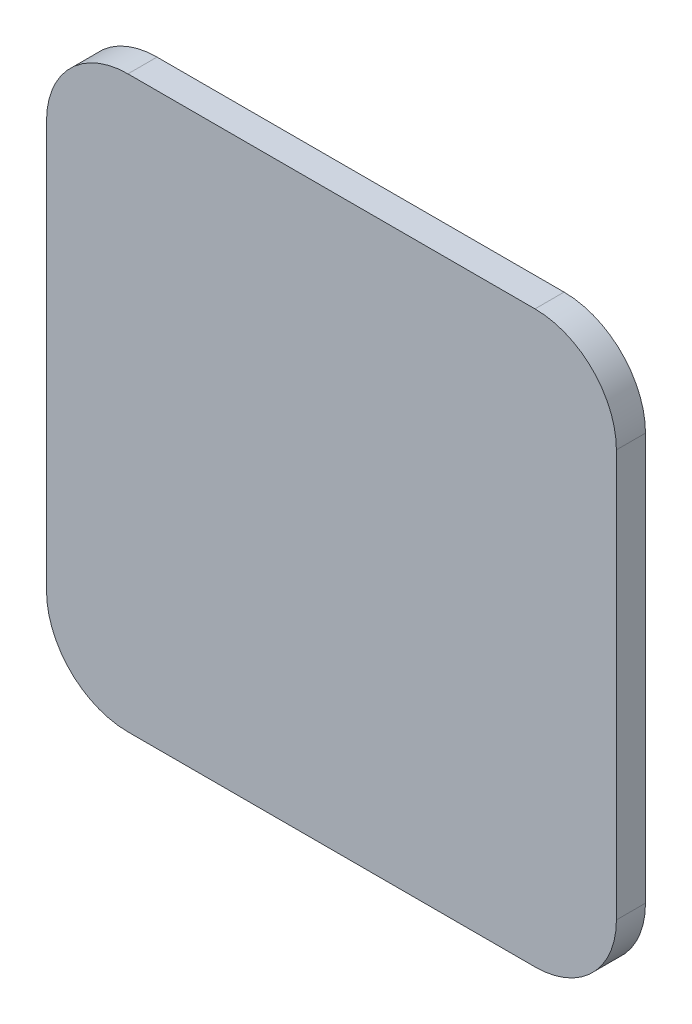
SolidWorks part; units mm, degrees
ref_plane "Front Plane" through (0, 0, 0) normal (0, 0, 1) x (1, 0, 0)
ref_plane "Top Plane" through (0, 0, 0) normal (0, 1, 0) x (1, 0, 0)
ref_plane "Right Plane" through (0, 0, 0) normal (1, 0, 0) x (0, 0, -1)
sketch "Sketch1" plane through (0, 0, 0) normal (0, 0, 1) x (1, 0, 0)
  line L0 (9.5027, -49.53) -> (9.5027, -31.75) construction
  line L1 (5.6927, -27.94) -> (-12.0873, -27.94) construction
  line L2 (5.6927, -53.34) -> (-12.0873, -53.34)
  line L3 (9.5027, -49.53) -> (9.5027, -31.75)
  line L4 (5.6927, -27.94) -> (-12.0873, -27.94)
  line L5 (-15.8973, -31.75) -> (-15.8973, -49.53)
  line L10 (6.5817, -49.53) -> (6.5817, -31.75)
  line L11 (5.6927, -30.861) -> (-12.0873, -30.861)
  line L12 (-12.9763, -31.75) -> (-12.9763, -49.53)
  line L13 (5.6927, -50.419) -> (-12.0873, -50.419)
  line L14 (5.6927, -28.194) -> (-12.0873, -28.194)
  line L15 (-15.6433, -31.75) -> (-15.6433, -49.53)
  line L16 (5.6927, -53.086) -> (-12.0873, -53.086)
  line L17 (9.2487, -49.53) -> (9.2487, -31.75)
  arc A0 (5.6927, -53.34) -> (9.5027, -49.53) centre (5.6927, -49.53) ccw
  arc A1 (9.5027, -31.75) -> (5.6927, -27.94) centre (5.6927, -31.75) ccw
  arc A2 (-12.0873, -27.94) -> (-15.8973, -31.75) centre (-12.0873, -31.75) ccw
  arc A3 (-12.0873, -27.94) -> (-15.8973, -31.75) centre (-12.0873, -31.75) ccw construction
  arc A4 (-12.0873, -53.34) -> (-15.8973, -49.53) centre (-12.0873, -49.53) cw
  arc A5 (-15.8973, -49.53) -> (-12.0873, -53.34) centre (-12.0873, -49.53) ccw construction
  arc A10 (6.5817, -31.75) -> (5.6927, -30.861) centre (5.6927, -31.75) ccw
  arc A11 (-12.0873, -30.861) -> (-12.9763, -31.75) centre (-12.0873, -31.75) ccw
  arc A12 (-12.0873, -50.419) -> (-12.9763, -49.53) centre (-12.0873, -49.53) cw
  arc A13 (5.6927, -50.419) -> (6.5817, -49.53) centre (5.6927, -49.53) ccw
  arc A14 (9.2487, -31.75) -> (5.6927, -28.194) centre (5.6927, -31.75) ccw
  arc A15 (-12.0873, -28.194) -> (-15.6433, -31.75) centre (-12.0873, -31.75) ccw
  arc A16 (-12.0873, -53.086) -> (-15.6433, -49.53) centre (-12.0873, -49.53) cw
  arc A17 (5.6927, -53.086) -> (9.2487, -49.53) centre (5.6927, -49.53) ccw
  dimension "D1" = 2.921
  dimension "D2" = 0.254
extrude "Boss-Extrude1" add sketch "Sketch1" against normal blind 1.27 contours L16 A17 L17 A14 L14 A15 L15 A16 A13 L13 A12 L12 A11 L11 A10 L10 region at (7.9583, -29.4844, 0)
extrude "Boss-Extrude2" add sketch "Sketch1<3>" against normal blind 2.54 contours L13 A13 L10 A10 L11 A11 L12 A12 region at (-3.1973, -40.64, 0)
sketch "Sketch1<3>" plane through (0, 0, 0) normal (0, 0, 1) x (1, 0, 0) same geometry as "Sketch1"
sketch "Sketch2" plane through (0, 0, -2.54) normal (0, 0, -1) x (-1, 0, 0)
  line L0 (12.0873, -30.861) -> (-5.6927, -30.861)
  line L1 (-6.5817, -31.75) -> (-6.5817, -49.53)
  line L2 (-5.6927, -50.419) -> (12.0873, -50.419)
  line L3 (12.9763, -49.53) -> (12.9763, -31.75)
  line L4 (11.7063, -49.149) -> (11.7063, -32.131)
  line L5 (11.7063, -32.131) -> (-5.3117, -32.131)
  line L6 (-5.3117, -32.131) -> (-5.3117, -49.149)
  line L7 (-5.3117, -49.149) -> (11.7063, -49.149)
  arc A0 (12.0873, -50.419) -> (12.9763, -49.53) centre (12.0873, -49.53) ccw
  arc A1 (12.0873, -50.419) -> (12.9763, -49.53) centre (12.0873, -49.53) ccw construction
  arc A2 (-6.5817, -49.53) -> (-5.6927, -50.419) centre (-5.6927, -49.53) ccw
  arc A3 (-6.5817, -49.53) -> (-5.6927, -50.419) centre (-5.6927, -49.53) ccw construction
  arc A4 (-5.6927, -30.861) -> (-6.5817, -31.75) centre (-5.6927, -31.75) ccw
  arc A5 (-5.6927, -30.861) -> (-6.5817, -31.75) centre (-5.6927, -31.75) ccw construction
  arc A6 (12.9763, -31.75) -> (12.0873, -30.861) centre (12.0873, -31.75) ccw
  arc A7 (12.9763, -31.75) -> (12.0873, -30.861) centre (12.0873, -31.75) ccw construction
  arc A8 (11.7063, -32.131) -> (11.7063, -32.131) centre (11.7063, -32.131) ccw
  arc A9 (-5.3117, -32.131) -> (-5.3117, -32.131) centre (-5.3117, -32.131) ccw
  arc A10 (-5.3117, -49.149) -> (-5.3117, -49.149) centre (-5.3117, -49.149) ccw
  arc A11 (11.7063, -49.149) -> (11.7063, -49.149) centre (11.7063, -49.149) ccw
  dimension "D1" = 1.27
extrude "Cut-Extrude1" cut sketch "Sketch2" against normal blind 1.778 contours L6 L7 L4 L5 region at (-3.1973, -40.64, -2.54)
